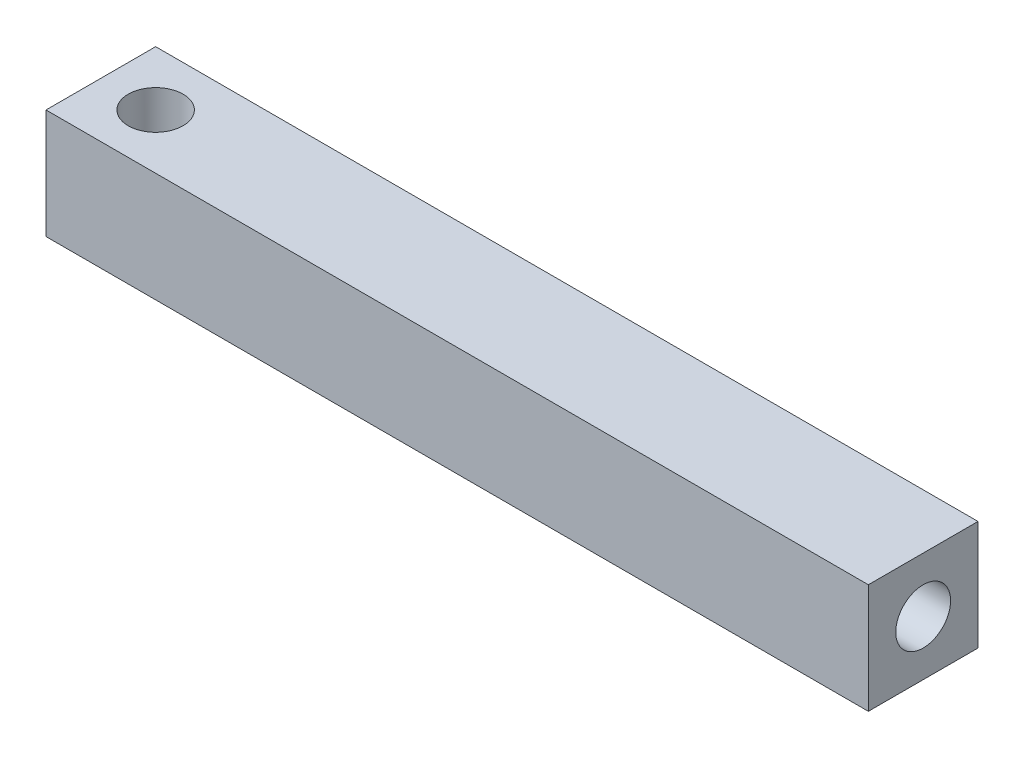
SolidWorks part; units mm, degrees
ref_plane "前视基准面" through (0, 0, 0) normal (0, 0, 1) x (1, 0, 0)
ref_plane "上视基准面" through (0, 0, 0) normal (0, 1, 0) x (1, 0, 0)
ref_plane "右视基准面" through (0, 0, 0) normal (1, 0, 0) x (0, 0, -1)
other "Configuration Table"
sketch "Sketch1" plane through (0, 0, 0) normal (1, 0, 0) x (0, 0, -1)
  line L1 (-20, -20) -> (20, -20)
  line L2 (-20, -20) -> (-20, 20)
  line L3 (-20, 20) -> (20, 20)
  line L4 (20, -20) -> (20, 20)
  line L5 (-20, -20) -> (20, 20) construction
  line L6 (-20, 20) -> (20, -20) construction
  point P0 (0, 0)
extrude "Boss-Extrude1" add sketch "Sketch1" along normal blind 300
sketch "Sketch2" plane through (0, 0, 0) normal (0, 1, 0) x (1, 0, 0)
  circle A0 centre (20, 0) radius 10
extrude "Cut-Extrude1" cut sketch "Sketch2" along normal blind 100 and the other way blind 100
ref_plane "Plane1" through (300, 0, 0) normal (1, 0, 0) x (0, 0, -1)
sketch "Sketch3" plane through (300, 0, 0) normal (1, 0, 0) x (0, 0, -1)
  circle A0 centre (0, 0) radius 10
extrude "Cut-Extrude2" cut sketch "Sketch3" along normal blind 50 and the other way blind 50
sketch3d "3DSketch1"
  line L0 (20, -50, 0) -> (20, 50, 0) construction
ref_axis "axis_3_conn" through (20, -50, 0) along (0, 1, 0)
sketch3d "3DSketch2"
  line L0 (250, 0, 0) -> (350, 0, 0) construction
ref_axis "axis_4_rot" through (250, 0, 0) along (1, 0, 0)
ref_plane "joint_face_3_conn" through (0, -20, 0) normal (0, 1, 0) x (1, 0, 0)
ref_plane "end_face" through (300, 0, 0) normal (1, 0, 0) x (0, 0, -1)
sketch "Sketch4" plane through (0, 0, 0) normal (1, 0, 0) x (0, 0, -1)
  line L1 (-20, -20) -> (20, -20)
  line L2 (-20, -20) -> (-20, 20)
  line L3 (-20, 20) -> (20, 20)
  line L4 (20, -20) -> (20, 20)
  line L5 (-20, -20) -> (20, 20) construction
  line L6 (-20, 20) -> (20, -20) construction
  point P0 (0, 0)
extrude "Boss-Extrude2" add sketch "Sketch4" along normal blind 300
sketch "Sketch5" plane through (0, 0, 0) normal (0, 1, 0) x (1, 0, 0)
  circle A0 centre (20, 0) radius 10
extrude "Cut-Extrude3" cut sketch "Sketch5" along normal blind 80 and the other way blind 80
ref_plane "Plane4" through (300, 0, 0) normal (1, 0, 0) x (0, 0, -1)
sketch "Sketch6" plane through (300, 0, 0) normal (1, 0, 0) x (0, 0, -1)
  circle A0 centre (0, 0) radius 10
extrude "Cut-Extrude4" cut sketch "Sketch6" against normal blind 30
sketch3d "3DSketch3"
  line L0 (20, -40, 0) -> (20, 40, 0) construction
ref_axis "Axis3" through (20, -40, 0) along (0, 1, 0)
sketch3d "3DSketch4"
  line L0 (250, 0, 0) -> (350, 0, 0) construction
ref_axis "Axis4" through (250, 0, 0) along (1, 0, 0)
ref_plane "Plane5" through (0, -20, 0) normal (0, 1, 0) x (1, 0, 0)
ref_plane "Plane6" through (300, 0, 0) normal (1, 0, 0) x (0, 0, -1)
